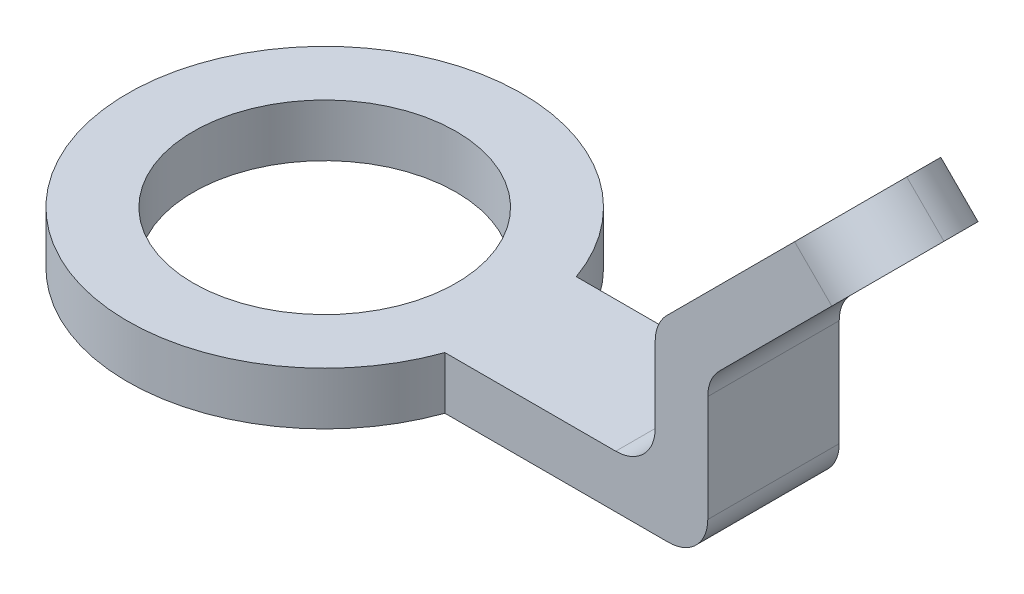
SolidWorks part; units mm, degrees
ref_plane "Front Plane" through (0, 0, 0) normal (0, 0, 1) x (1, 0, 0)
ref_plane "Top Plane" through (0, 0, 0) normal (0, 1, 0) x (1, 0, 0)
ref_plane "Right Plane" through (0, 0, 0) normal (1, 0, 0) x (0, 0, -1)
sketch "Sketch2" plane through (0, 0, 0) normal (0, 1, 0) x (1, 0, 0)
  line L0 (0, 0) -> (34.1421, 0) construction
  line L1 (34.1421, 5) -> (34.1421, -5)
  line L2 (34.1421, -5) -> (14.1421, -5)
  line L3 (34.1421, 5) -> (14.1421, 5)
  arc A0 (14.1421, 5) -> (14.1421, -5) centre (0, 0) ccw
  circle A1 centre (0, 0) radius 10
  dimension "D1" = 30
  dimension "D5" = 20
  dimension "D2" = 5
  dimension "D3" = 5
  dimension "D4" = 20
extrude "Boss-Extrude1" add sketch "Sketch2" along normal blind 4
sketch "Sketch3" plane through (0, 0, 5) normal (0, 0, 1) x (1, 0, 0)
  line L0 (34.1421, 4) -> (34.1421, 12.3431)
  line L1 (34.1421, 12.3431) -> (47.1127, 25.3137)
  line L2 (47.1127, 25.3137) -> (44.2843, 28.1421)
  line L3 (44.2843, 28.1421) -> (30.1421, 14)
  line L4 (30.1421, 14) -> (30.1421, 4)
  line L5 (14.1421, 4) -> (34.1421, 4) construction
  line L6 (30.1421, 4) -> (34.1421, 4)
  dimension "D1" = 4
  dimension "D2" = 4
  dimension "D3" = 135
  dimension "D4" = 10
  dimension "D5" = 20
extrude "Boss-Extrude2" add sketch "Sketch3" against normal blind 10
sketch "Sketch4" plane through (0, 0, 0) normal (0, -1, 0) x (1, 0, 0)
  circle A0 centre (0, 0) radius 12
  circle A1 centre (0, 0) radius 13
  dimension "D1" = 24
  dimension "D2" = 26
extrude "Boss-Extrude3" [suppressed] add sketch "Sketch4" along normal blind 1
fillet "Fillet1" radius 5 2 edges at (45.6985, 26.7279, -5) (45.6985, 26.7279, 5)
sketch "Sketch5" plane through (8.0711, -8.0711, 0) normal (-0.7071, 0.7071, 0) x (0.7071, 0.7071, 0)
  circle A0 centre (46.2132, 0) radius 2.5
  dimension "D1" = 5
hole_wizard "M3 Clearance Hole1" positions "Sketch6" profile "Sketch7" hole size "M3" standard "ANSI Metric" end condition through all
sketch "Sketch6" plane through (8.0711, -8.0711, 0) normal (-0.7071, 0.7071, 0) x (0.7071, 0.7071, 0)
  point P0 (46.2132, 0)
sketch "Sketch7" plane through (40.7487, 24.6066, 0) normal (0, 0, 1) x (-0.7071, -0.7071, 0)
  line L0 (0, 0) -> (0, 21.8995)
  line L1 (0, 21.8995) -> (1.8, 21.8995)
  line L2 (1.8, 21.8995) -> (1.8, 0)
  line L5 (1.8, 0) -> (0, 0)
  line L11 (0, -6.35) -> (0, 107.95) construction
  dimension "Thru Hole Dia." = 3.6
  dimension "Thru Hole Depth" = 21.8995
fillet "Fillet2" radius 3 4 edges at (34.1421, 12.3431, 0) (30.1421, 14, 0) (34.1421, 0, 0) (30.1421, 4, 0)
